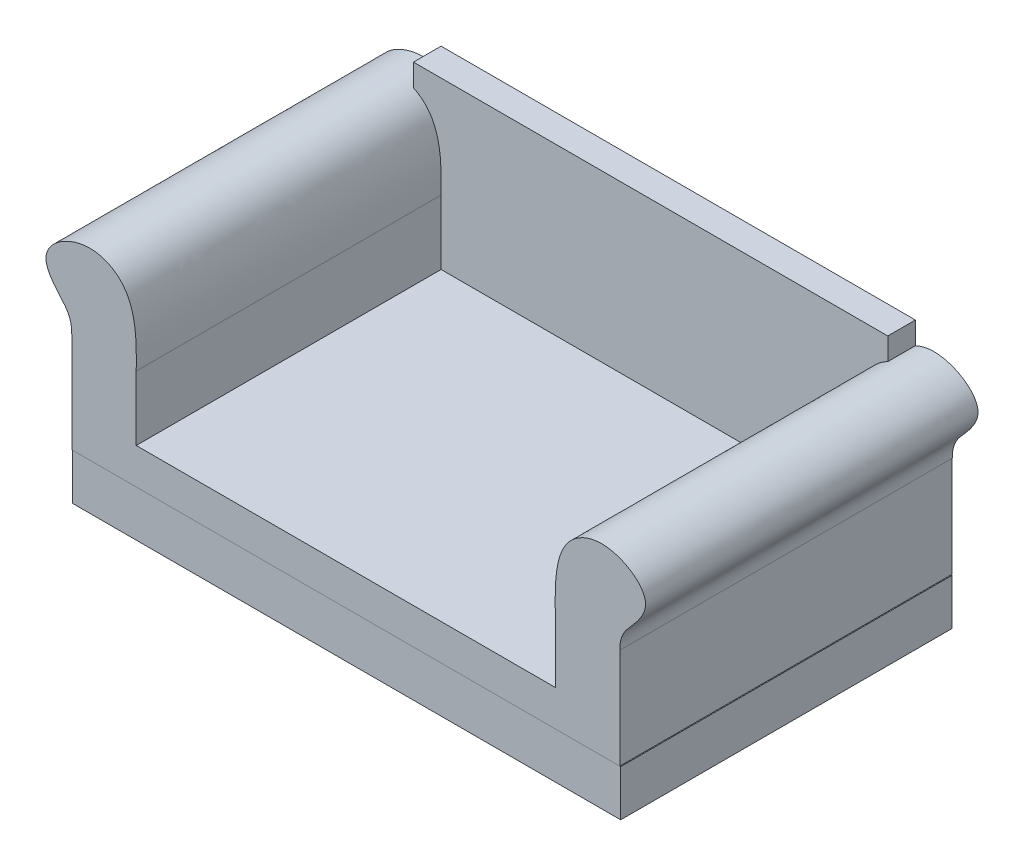
SolidWorks part; units mm, degrees
ref_plane "Front Plane" through (0, 0, 0) normal (0, 0, 1) x (1, 0, 0)
ref_plane "Top Plane" through (0, 0, 0) normal (0, 1, 0) x (1, 0, 0)
ref_plane "Right Plane" through (0, 0, 0) normal (1, 0, 0) x (0, 0, -1)
sketch "Sketch1" plane through (0, 0, 0) normal (0, 1, 0) x (1, 0, 0)
  line L1 (-755.65, -457.2) -> (755.65, -457.2) construction
  line L2 (-755.65, -457.2) -> (-755.65, 457.2) construction
  line L3 (-755.65, 457.2) -> (755.65, 457.2) construction
  line L4 (755.65, -457.2) -> (755.65, 457.2) construction
  line L5 (-755.65, -457.2) -> (755.65, 457.2) construction
  line L6 (-755.65, 457.2) -> (755.65, -457.2) construction
  line L7 (-755.65, 457.2) -> (-666.75, 457.2)
  line L8 (-755.65, 457.2) -> (-755.65, -457.2)
  line L9 (-755.65, -457.2) -> (-666.75, -457.2)
  line L10 (-666.75, 457.2) -> (-666.75, -457.2)
  line L11 (-711.2, -457.2) -> (-711.2, 457.2) construction
  line L12 (-755.65, 0) -> (-666.75, 0) construction
  line L13 (666.75, 457.2) -> (755.65, 457.2)
  line L14 (666.75, 457.2) -> (666.75, -457.2)
  line L15 (666.75, -457.2) -> (755.65, -457.2)
  line L16 (755.65, 457.2) -> (755.65, -457.2)
  line L17 (711.2, -457.2) -> (711.2, 457.2) construction
  line L18 (666.75, 0) -> (755.65, 0) construction
  line L19 (-666.75, 431.8) -> (666.75, 431.8)
  line L20 (-666.75, 431.8) -> (-666.75, 457.2)
  line L21 (-666.75, 457.2) -> (666.75, 457.2)
  line L22 (666.75, 431.8) -> (666.75, 457.2)
  line L23 (0, 457.2) -> (0, 431.8) construction
  line L24 (-666.75, 444.5) -> (666.75, 444.5) construction
  line L25 (-666.75, -457.2) -> (666.75, -457.2)
  line L26 (-666.75, -457.2) -> (-666.75, -431.8)
  line L27 (-666.75, -431.8) -> (666.75, -431.8)
  line L28 (666.75, -457.2) -> (666.75, -431.8)
  line L29 (0, -431.8) -> (0, -457.2) construction
  line L30 (-666.75, -444.5) -> (666.75, -444.5) construction
  line L31 (31.75, 431.8) -> (57.15, 431.8)
  line L32 (31.75, 431.8) -> (31.75, -431.8)
  line L33 (31.75, -431.8) -> (57.15, -431.8)
  line L34 (57.15, 431.8) -> (57.15, -431.8)
  line L35 (44.45, -431.8) -> (44.45, 431.8) construction
  line L36 (31.75, 0) -> (57.15, 0) construction
  point P0 (0, 0)
  point P22 (711.2, 0)
  point P23 (0, 0)
  point P24 (711.2, 0)
  point P25 (755.65, 457.2)
  point P26 (-666.75, 0)
  point P27 (666.75, 457.2)
  point P28 (0, 0)
  point P29 (711.2, 0)
  point P140 (711.2, 0)
  point P190 (44.45, 0)
  point P309 (0, -444.5)
  point P335 (0, 444.5)
  point P376 (-711.2, 0)
  dimension "D1" = 914.4
  dimension "D3" = 88.9
  dimension "D4" = 25.4
  dimension "D5" = 25.4
  dimension "D6" = 25.4
  dimension "D7" = 787.4
  dimension "D2" = 698.5
extrude "Boss-Extrude1" add sketch "Sketch1" along normal blind 127 contours L10 L7 L8 L9 | L27 L10 L25 L14 | L16 L13 L14 L15 | L21 L10 L19 L14 | L34 L19 L32 L27 region at (-711.2, 0, 0) region at (0, 0, -444.5) region at (711.2, 0, 0) region at (0, 0, 444.5) region at (44.45, 0, 0)
ref_plane "Plane1" through (0, 129.54, 0) normal (0, 1, 0) x (1, 0, 0)
sketch "Sketch2" plane through (0, 129.54, 0) normal (0, 1, 0) x (1, 0, 0)
  line L0 (755.65, 457.2) -> (755.65, -457.2) construction
  line L1 (-755.65, -457.2) -> (755.65, -457.2) construction
  line L2 (-755.65, 457.2) -> (-755.65, -457.2) construction
  line L3 (-755.65, 457.2) -> (755.65, 457.2) construction
  line L4 (755.65, 457.2) -> (755.65, -457.2)
  line L5 (-755.65, -457.2) -> (755.65, -457.2)
  line L6 (-755.65, 457.2) -> (-755.65, -457.2)
  line L7 (-755.65, 457.2) -> (755.65, 457.2)
ref_plane "Plane2" through (0, 0, 459.74) normal (0, 0, 1) x (1, 0, 0)
sketch "Sketch4" plane through (0, 0, 459.74) normal (0, 0, 1) x (1, 0, 0)
  line L0 (-755.65, 129.54) -> (755.65, 129.54) construction
  line L4 (-755.65, 0) -> (755.65, 0) construction
  line L5 (755.65, 0) -> (755.65, 127) construction
  line L6 (755.65, 127) -> (-755.65, 127) construction
  line L7 (-755.65, 127) -> (-755.65, 0) construction
  line L8 (-755.65, 129.54) -> (755.65, 129.54)
  line L12 (-755.65, 0) -> (755.65, 0)
  line L13 (755.65, 0) -> (755.65, 127)
  line L14 (755.65, 127) -> (-755.65, 127)
  line L15 (-755.65, 127) -> (-755.65, 0)
  line L16 (-755.65, 129.54) -> (-755.65, 406.4)
  line L17 (-577.85, 406.4) -> (-577.85, 228.6)
  line L18 (-577.85, 228.6) -> (577.85, 228.6)
  line L19 (0, 0) -> (0, 50000) construction
  line L20 (577.85, 406.4) -> (577.85, 228.6)
  line L21 (755.65, 129.54) -> (755.65, 406.4)
  spline S0 degree 3 poles (-755.65, 406.4) (-755.65, 451.0873) (-791.2169, 477.4334) (-855.3989, 573.8525) (-720.3037, 663.2325) (-568.8677, 589.8389) (-577.85, 447.6507) (-577.85, 406.4) knots 0 0 0 0 0.157243 0.266643 0.492649 0.701572 1 1 1 1
  spline S1 degree 3 poles (755.65, 406.4) (755.65, 451.0873) (791.2169, 477.4334) (855.3989, 573.8525) (720.3037, 663.2325) (568.8677, 589.8389) (577.85, 447.6507) (577.85, 406.4) knots 0 0 0 0 0.157243 0.266643 0.492649 0.701572 1 1 1 1
  point P3 (0, 0)
  point P4 (-610.4861, 555.1521)
  point P15 (-826.7026, 549.9064)
  point P16 (0, 0)
  point P17 (-798.8978, 593.6998)
  point P18 (-748.1425, 754.1521)
  point P19 (-636.8082, 637.9061)
  point P20 (0, 0)
  point P21 (-823.4568, 492.1892)
  point P23 (-815.2705, 588.788)
  point P25 (-674.4654, 596.9743)
  point P27 (-828.3686, 582.2389)
  point P28 (0, 0)
  point P29 (0, 0)
  point P30 (0, 0)
  point P31 (-797.2605, 495.4637)
  point P32 (-795.6232, 479.091)
  point P33 (-644.9945, 554.4054)
  point P34 (-836.555, 567.5035)
  point P35 (-720.9599, 635)
  point P36 (-829.1322, 581.6197)
  point P37 (-601.28, 548.2475)
  point P38 (0, 0)
  point P39 (-831.4337, 551.6998)
  point P47 (0, 228.6)
  point P48 (-606.6389, 583.2953)
  point P49 (-800.5343, 488.1332)
  point P50 (-797.3102, 491.1467)
  dimension "D1" = 635
  dimension "D2" = 406.4
  dimension "D3" = 228.6
  dimension "D4" = 177.8
extrude "Boss-Extrude3" add sketch "Sketch4" against normal up to surface (916.94 mm away) separate body contours S0 L17 L18 L20 S1 L21 L8 L16 up to face at (0, 63.5, -457.2)
sketch "Sketch5" plane through (0, 228.6, 0) normal (0, 1, 0) x (1, 0, 0)
  line L0 (-755.65, 457.2) -> (755.65, 457.2) construction
  line L1 (-654.05, 457.2) -> (654.05, 457.2)
  line L2 (-654.05, 457.2) -> (-654.05, 381)
  line L3 (-654.05, 381) -> (654.05, 381)
  line L4 (577.85, 457.2) -> (-577.85, 457.2)
  line L5 (-577.85, 457.2) -> (-577.85, -459.74)
  line L6 (-577.85, -459.74) -> (577.85, -459.74)
  line L7 (577.85, -459.74) -> (577.85, 457.2)
  line L8 (577.85, 457.2) -> (-577.85, 457.2)
  line L9 (-577.85, 457.2) -> (-577.85, -459.74)
  line L10 (-577.85, -459.74) -> (577.85, -459.74)
  line L11 (577.85, -459.74) -> (577.85, 457.2)
  line L12 (654.05, 457.2) -> (654.05, 381)
  line L13 (0, 381) -> (0, 457.2) construction
  line L14 (-654.05, 419.1) -> (654.05, 419.1) construction
  point P112 (0, 419.1)
  dimension "D2" = 76.2
  dimension "D3" = 76.2
  dimension "D1" = 0
extrude "Boss-Extrude4" add sketch "Sketch5" along normal blind 457.2 contours L1 L12 L3 L2
equation "\"D5@Sketch1\"=\"D4@Sketch1\""
